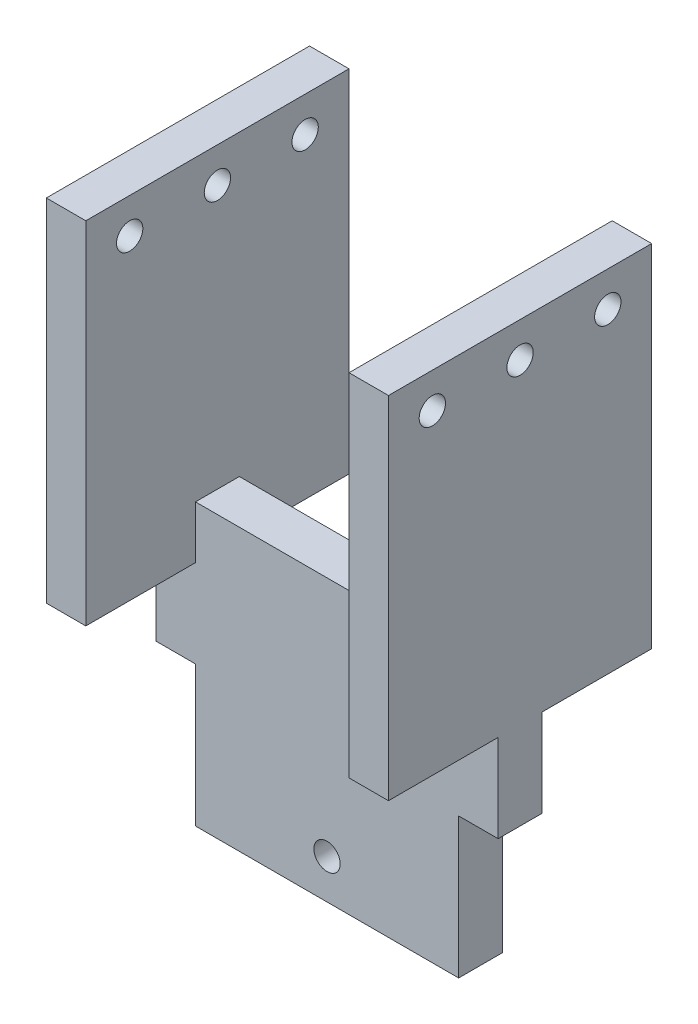
SolidWorks part; units mm, degrees
ref_plane "前视基准面" through (0, 0, 0) normal (0, 0, 1) x (1, 0, 0)
ref_plane "上视基准面" through (0, 0, 0) normal (0, 1, 0) x (1, 0, 0)
ref_plane "右视基准面" through (0, 0, 0) normal (1, 0, 0) x (0, 0, -1)
sketch "草图1" plane through (0, 0, 0) normal (0, 0, 1) x (1, 0, 0)
  line L1 (15, -25) -> (-15, -25)
  line L2 (15, -25) -> (15, 25)
  line L3 (15, 25) -> (-15, 25)
  line L4 (-15, -25) -> (-15, 25)
  line L5 (15, -25) -> (-15, 25) construction
  line L6 (15, 25) -> (-15, -25) construction
  point P0 (0, 0)
  dimension "D1" = 30
  dimension "D2" = 50
extrude "凸台-拉伸1" add sketch "草图1" along normal blind 5
sketch "草图5" plane through (-15, 0, 0) normal (-1, 0, 0) x (0, 0, 1)
  line L0 (5, 25) -> (0, 25) construction
  line L1 (17.5, 9) -> (-12.5, 9)
  line L2 (17.5, 9) -> (17.5, 59)
  line L3 (17.5, 59) -> (-12.5, 59)
  line L4 (-12.5, 9) -> (-12.5, 59)
  line L5 (17.5, 9) -> (-12.5, 59) construction
  line L6 (17.5, 59) -> (-12.5, 9) construction
  line L7 (2.5, -25) -> (2.5, 25) construction
  line L8 (5, -25) -> (0, -25) construction
  line L9 (2.5, 25) -> (2.5, 40.0267) construction
  point P0 (2.5, 34)
  dimension "D1" = 16
  dimension "D2" = 30
  dimension "D3" = 50
extrude "凸台-拉伸2" add sketch "草图5" along normal blind 4.5
mirror "镜向1" about plane through (0, 0, 0) normal (1, 0, 0) of "凸台-拉伸2"
sketch "草图6" plane through (-19.5, 0, 0) normal (-1, 0, 0) x (0, 0, 1)
  line L0 (2.5, 59) -> (2.5, 55) construction
  line L1 (17.5, 59) -> (-12.5, 59) construction
  circle A0 centre (2.5, 55) radius 1.5
  dimension "D1" = 4
  dimension "D2" = 3
extrude "切除-拉伸1" cut sketch "草图6" against normal through all
sketch "草图7" plane through (-19.5, 0, 0) normal (-1, 0, 0) x (0, 0, 1)
  line L0 (2.5, 55) -> (-7.5, 55) construction
  line L1 (2.5, 55) -> (12.5, 55) construction
  circle A0 centre (-7.5, 55) radius 1.5
  circle A1 centre (12.5, 55) radius 1.5
  dimension "D3" = 3
  dimension "D4" = 3
  dimension "D1" = 10
  dimension "D2" = 10
extrude "切除-拉伸2" cut sketch "草图7" against normal through all
sketch "草图9" plane through (0, 0, 5) normal (0, 0, 1) x (1, 0, 0)
  line L0 (0, -25) -> (0, -19) construction
  line L1 (-15, -25) -> (15, -25) construction
  circle A0 centre (0, -19) radius 1.5
  dimension "D2" = 3
  dimension "D1" = 6
sketch "草图10" plane through (0, 0, 0) normal (0, 0, -1) x (-1, 0, 0)
  line L0 (0, -13.5) -> (0, -2.5) construction
  circle A0 centre (0, -13.5) radius 1.5
  circle A1 centre (0, -2.5) radius 1.5
  dimension "D1" = 3
  dimension "D2" = 3
  dimension "D3" = 11
extrude "切除-拉伸3" cut sketch "草图10" against normal through all
sketch "草图11" plane through (0, 0, 0) normal (0, 0, -1) x (-1, 0, 0)
  line L0 (-15, -25) -> (-15, 9) construction
  line L1 (15, -25) -> (-15, -25)
  line L2 (15, -25) -> (15, 3)
  line L3 (15, 3) -> (-15, 3)
  line L4 (-15, -25) -> (-15, 3)
  dimension "D1" = 28
sketch "草图12" plane through (-15, 0, 0) normal (1, 0, 0) x (0, 0, -1)
  line L0 (12.5, 59) -> (12.5, 9) construction
  line L1 (0, 9) -> (12.5, 9)
  line L2 (0, 9) -> (0, 19)
  line L3 (0, 19) -> (12.5, 19)
  line L4 (12.5, 9) -> (12.5, 19)
  line L5 (-17.5, 9) -> (-17.5, 59) construction
  line L6 (-5, 9) -> (-17.5, 9)
  line L7 (-5, 9) -> (-5, 19)
  line L8 (-5, 19) -> (-17.5, 19)
  line L9 (-17.5, 9) -> (-17.5, 19)
  dimension "D1" = 10
  dimension "D2" = 10
sketch "草图13" plane through (15, 0, 0) normal (-1, 0, 0) x (0, 0, 1)
  line L0 (17.5, 11) -> (17.5, 57) construction
  line L1 (5, 9) -> (17.5, 9)
  line L2 (5, 9) -> (5, 19)
  line L3 (5, 19) -> (17.5, 19)
  line L4 (17.5, 9) -> (17.5, 19)
  line L5 (-12.5, 57) -> (-12.5, 11) construction
  line L6 (0, 9) -> (-12.5, 9)
  line L7 (0, 9) -> (0, 19)
  line L8 (0, 19) -> (-12.5, 19)
  line L9 (-12.5, 9) -> (-12.5, 19)
  dimension "D1" = 10
  dimension "D2" = 10
sketch "草图14" plane through (0, 0, 0) normal (0, 0, -1) x (-1, 0, 0)
  line L1 (-15, -25) -> (23.6948, -25)
  line L2 (-15, -25) -> (-15, -7)
  line L3 (-15, -7) -> (23.6948, -7)
  line L4 (23.6948, -25) -> (23.6948, -7)
  dimension "D1" = 18
extrude "切除-拉伸7" cut sketch "草图14" against normal through all
extrude "切除-拉伸8" cut sketch "草图12" against normal through all
extrude "切除-拉伸9" cut sketch "草图13" against normal through all
